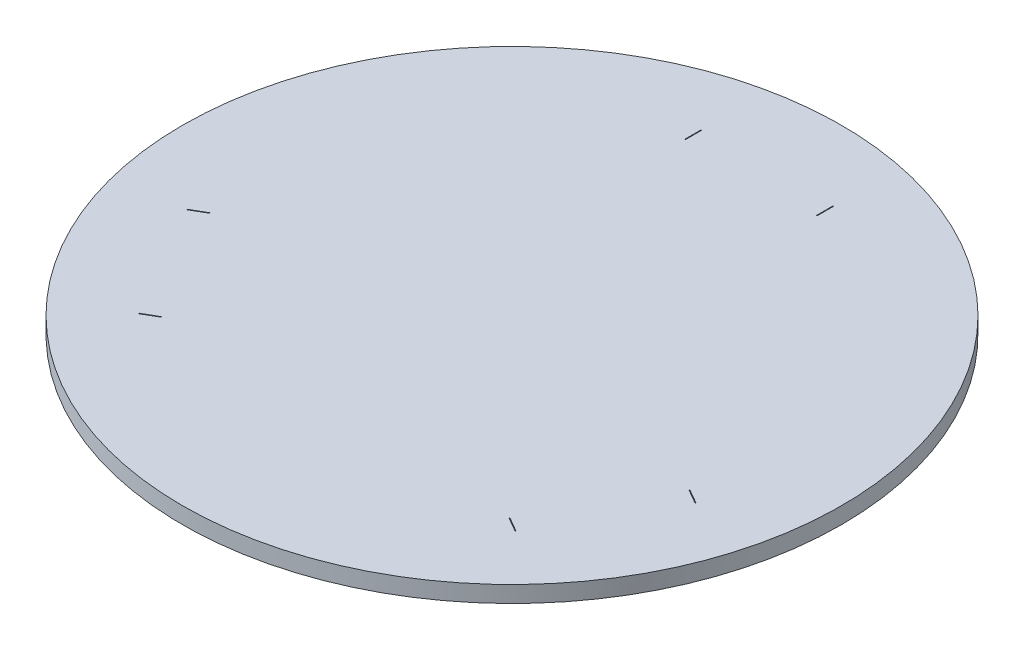
SolidWorks part; units mm, degrees
ref_plane "Front Plane" through (0, 0, 0) normal (0, 0, 1) x (1, 0, 0)
ref_plane "Top Plane" through (0, 0, 0) normal (0, 1, 0) x (1, 0, 0)
ref_plane "Right Plane" through (0, 0, 0) normal (1, 0, 0) x (0, 0, -1)
sketch "Sketch2" plane through (0, 0, 0) normal (0, 1, 0) x (1, 0, 0)
  circle A0 centre (0, 0) radius 100
  dimension "D1" = 200
extrude "Boss-Extrude1" add sketch "Sketch2" along normal blind 5
sketch "Sketch3" plane through (0, 5, 0) normal (0, 1, 0) x (1, 0, 0)
  line L0 (0, 0) -> (0, 100) construction
  line L1 (-20, 75) -> (20, 75) construction
  line L2 (72.8368, -18.8429) -> (77.167, -21.3429)
  line L3 (-20.1, 72.5) -> (-19.9, 72.5)
  line L4 (-20.1, 72.5) -> (-20.1, 77.5)
  line L5 (-20.1, 77.5) -> (-19.9, 77.5)
  line L6 (-19.9, 72.5) -> (-19.9, 77.5)
  line L7 (-20.1, 72.5) -> (-19.9, 77.5) construction
  line L8 (-20.1, 77.5) -> (-19.9, 72.5) construction
  line L9 (19.9, 72.5) -> (20.1, 72.5)
  line L10 (19.9, 72.5) -> (19.9, 77.5)
  line L11 (19.9, 77.5) -> (20.1, 77.5)
  line L12 (20.1, 72.5) -> (20.1, 77.5)
  line L13 (19.9, 72.5) -> (20.1, 77.5) construction
  line L14 (19.9, 77.5) -> (20.1, 72.5) construction
  line L15 (72.8368, -18.8429) -> (72.7368, -19.0161)
  line L16 (72.7368, -19.0161) -> (77.067, -21.5161)
  line L17 (77.167, -21.3429) -> (77.067, -21.5161)
  line L18 (52.8368, -53.4839) -> (57.167, -55.9839)
  line L19 (52.8368, -53.4839) -> (52.7368, -53.6571)
  line L20 (52.7368, -53.6571) -> (57.067, -56.1571)
  line L21 (57.167, -55.9839) -> (57.067, -56.1571)
  line L22 (-52.7368, -53.6571) -> (-57.067, -56.1571)
  line L23 (-52.7368, -53.6571) -> (-52.8368, -53.4839)
  line L24 (-52.8368, -53.4839) -> (-57.167, -55.9839)
  line L25 (-57.067, -56.1571) -> (-57.167, -55.9839)
  line L26 (-72.7368, -19.0161) -> (-77.067, -21.5161)
  line L27 (-72.7368, -19.0161) -> (-72.8368, -18.8429)
  line L28 (-72.8368, -18.8429) -> (-77.167, -21.3429)
  line L29 (-77.067, -21.5161) -> (-77.167, -21.3429)
  line L30 (0, 0) -> (-86.6025, -50) construction
  line L31 (-74.9019, -20.2661) -> (-55.0019, -54.7339) construction
  line L32 (0, 0) -> (86.6025, -50) construction
  line L33 (74.9019, -20.2661) -> (55.0019, -54.7339) construction
  circle A0 centre (0, 0) radius 100 construction
  point P8 (0, 75)
  point P36 (0, 0)
  dimension "D1" = 40
  dimension "D2" = 5
  dimension "D3" = 0.2
  dimension "D4" = 75
  dimension "D6" = 120
  dimension "D7" = 120
  dimension "D5" = 3
extrude "Cut-Extrude1" cut sketch "Sketch3" against normal through all
sketch "Sketch4" plane through (0, 0, 0) normal (0, 0, 1) x (1, 0, 0)
  line L0 (-100, 0) -> (0, 0)
  line L1 (0, 0) -> (0, -31.5299)
  line L2 (0, -31.5299) -> (26.4846, -31.5299) construction
  line L3 (-100, 0) -> (-128.8281, 20.1856) construction
  arc A0 (0, -31.5299) -> (-100, 0) centre (0, 142.8148) cw
  dimension "D1" = 35
revolve "Revolve1" add sketch "Sketch4" angle 360 about L1
equation "\"Leg_Spacing\"=40"
equation "\"D1@Sketch3\"=\"Leg_Spacing\""
equation "\"Leaf_Spring_Slot_Width\"=5"
equation "\"D2@Sketch3\"=\"Leaf_Spring_Slot_Width\""
equation "\"Leaf_Spring_Thickness\"=0.2"
equation "\"D3@Sketch3\"=\"Leaf_Spring_Thickness\""
equation "\"Inner_Radius\"=75"
equation "\"D4@Sketch3\"=\"Inner_Radius\""
equation "\"Camera\"=120"
